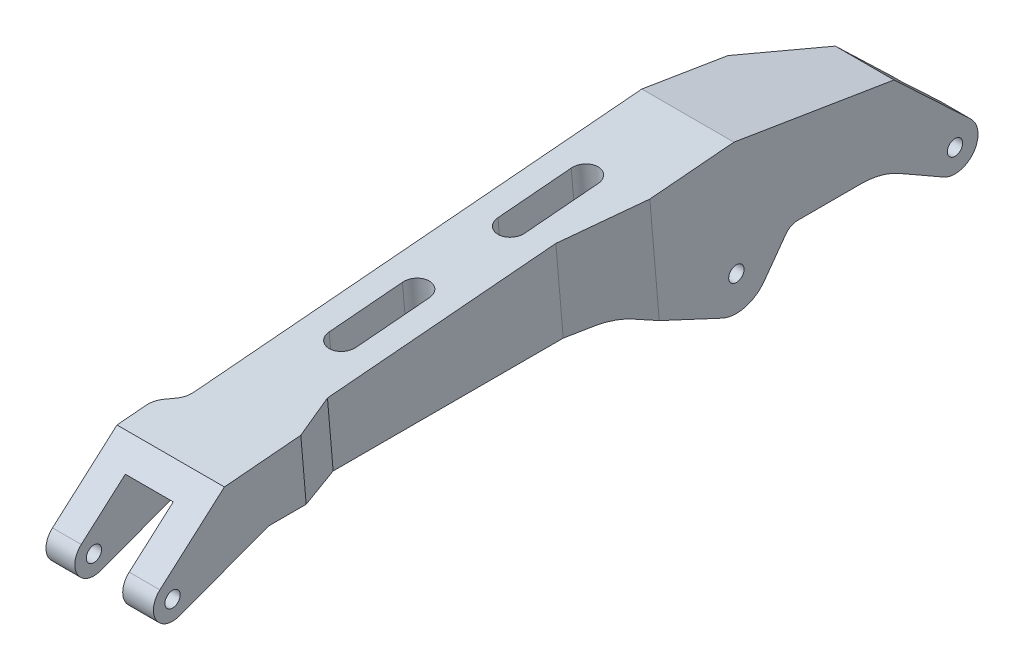
SolidWorks part; units mm, degrees
ref_plane "Plan de face" through (0, 0, 0) normal (0, 0, 1) x (1, 0, 0)
ref_plane "Plan de dessus" through (0, 0, 0) normal (0, 1, 0) x (1, 0, 0)
ref_plane "Plan de droite" through (0, 0, 0) normal (1, 0, 0) x (0, 0, -1)
sketch "Sketch1" plane through (0, 0, 0) normal (1, 0, 0) x (0, 0, -1)
  line L0 (-121.9079, 4) -> (-145.2566, -4.6862)
  line L8 (-34.3077, 4) -> (-121.9079, 4)
  line L12 (-3.8036, -8.1568) -> (-25.8554, 2.1262)
  line L13 (12.8503, 2.4104) -> (7.2926, -5.2742)
  line L15 (32.5383, 4.0311) -> (16.0227, 4.0311)
  line L16 (54.0258, -5.2082) -> (42.4563, 1.3987)
  line L17 (41.089, 23.1881) -> (61.1079, 4.37)
  line L22 (-0.6535, 30.0125) -> (41.089, 23.1881)
  line L24 (-133.4914, 18.5783) -> (-0.6535, 30.0125)
  line L29 (-150.307, 3.7502) -> (-133.4914, 18.5783)
  arc A10 (-25.8554, 2.1262) -> (-34.3077, 4) centre (-34.3077, -16) ccw
  arc A11 (-3.8036, -8.1568) -> (7.2926, -5.2742) centre (0, 0) ccw
  arc A12 (42.4563, 1.3987) -> (32.5383, 4.0311) centre (32.5383, -15.9689) ccw
  arc A13 (54.0258, -5.2082) -> (61.1079, 4.37) centre (57, 0) ccw
  arc A17 (-150.307, 3.7502) -> (-145.2566, -4.6862) centre (-147, 0) ccw
  arc A18 (12.8503, 2.4104) -> (16.0227, 4.0311) centre (16.0227, 0.1161) cw
  circle A19 centre (0, 0) radius 2
  circle A20 centre (57, 0) radius 2
  circle A21 centre (-147, 0) radius 2
  dimension "D1" = 4
  dimension "D2" = 5
  dimension "D3" = 9
  dimension "D4" = 5.9976
  dimension "D5" = 57
  dimension "D6" = 147
  dimension "D7" = 24.9122
  dimension "D8" = 22.4195
  dimension "D9" = 24.3315
  dimension "D10" = 9.4837
  dimension "D11" = 27.475
  dimension "D12" = 42.2967
  dimension "D13" = 21
  dimension "D14" = 13.5
extrude "Boss-Extrude1" add sketch "Sketch1" along normal mid plane 24
sketch "Sketch2" plane through (0, 29.1272, -4.7619) normal (0, 0.9869, -0.1613) x (1, 0, 0)
  line L0 (12, 62.2508) -> (-12, 62.2508) construction
  line L1 (-12, 62.2508) -> (-12, 54.1582) construction
  line L2 (-12, 59.6022) -> (-12, 36.8094) construction
  line L3 (3.5, 62.2508) -> (-12, 62.2508) construction
  line L4 (-12, 62.2508) -> (-12, 54.1582) construction
  line L5 (-12, 59.6022) -> (-12, 36.8094) construction
  line L6 (-12, 36.8094) -> (-12, -5.4873) construction
  line L7 (-12, 36.8094) -> (-12, 17.2508) construction
  line L8 (3.5, 62.2508) -> (3.5, 52.0644)
  line L9 (3.5, 52.0644) -> (-12, 17.2508)
  line L10 (12, 59.6022) -> (12, 36.8094) construction
  line L11 (-12, 17.2508) -> (-12, 62.2508)
  line L12 (-12, 62.2508) -> (3.5, 62.2508)
  dimension "D1" = 8.5
  dimension "D2" = 156
  dimension "D3" = 45
extrude "Cut-Extrude1" cut sketch "Sketch2" against normal through all
sketch "Sketch5" plane through (-12, 0, 0) normal (-1, 0, 0) x (0, 0, 1)
  line L0 (145.2566, -4.6862) -> (121.9079, 4) construction
  line L1 (133.4914, 18.5783) -> (150.307, 3.7502) construction
  line L2 (145.2566, -4.6862) -> (121.9079, 4)
  line L3 (133.4914, 18.5783) -> (150.307, 3.7502)
  line L4 (133.4914, 18.5783) -> (120.4914, 19.6973)
  line L5 (0.6535, 30.0125) -> (133.4914, 18.5783) construction
  line L6 (120.4914, 19.6973) -> (108.9079, 4)
  line L7 (121.9079, 4) -> (34.3077, 4) construction
  line L8 (108.9079, 4) -> (121.9079, 4)
  arc A0 (145.2566, -4.6862) -> (150.307, 3.7502) centre (147, 0) ccw construction
  circle A1 centre (147, 0) radius 2 construction
  arc A2 (145.2566, -4.6862) -> (150.307, 3.7502) centre (147, 0) ccw
  circle A3 centre (147, 0) radius 2
  dimension "D1" = 13
  dimension "D2" = 13
extrude "Boss-Extrude3" add sketch "Sketch5" along normal blind 4
ref_plane "Plane1" through (4, 0, 0) normal (1, 0, 0) x (0, 0, -1)
sketch "Sketch6" plane through (4, 0, 0) normal (1, 0, 0) x (0, 0, -1)
  line L0 (-150.307, 3.7502) -> (-138.8214, 13.8783)
  line L2 (-121.9079, 4) -> (-145.2566, -4.6862)
  line L3 (-145.2566, -4.6862) -> (-121.9079, 4) construction
  line L4 (-133.4914, 18.5783) -> (-150.307, 3.7502) construction
  line L5 (-138.8214, 13.8783) -> (50.9929, 13.8783)
  line L6 (-121.9079, 4) -> (-34.3077, 4) construction
  line L7 (-121.9079, 4) -> (-34.3077, 4)
  line L8 (16.0227, 4.0311) -> (32.5383, 4.0311) construction
  line L9 (7.2926, -5.2742) -> (12.8503, 2.4104) construction
  line L10 (-25.8554, 2.1262) -> (-3.8036, -8.1568) construction
  line L11 (16.0227, 4.0311) -> (32.5383, 4.0311)
  line L12 (7.2926, -5.2742) -> (12.8503, 2.4104)
  line L13 (-25.8554, 2.1262) -> (-3.8036, -8.1568)
  line L14 (61.1079, 4.37) -> (41.089, 23.1881) construction
  line L15 (42.4563, 1.3987) -> (54.0258, -5.2082) construction
  line L16 (61.1079, 4.37) -> (50.9929, 13.8783)
  line L17 (42.4563, 1.3987) -> (54.0258, -5.2082)
  arc A0 (-150.307, 3.7502) -> (-145.2566, -4.6862) centre (-147, 0) ccw construction
  arc A1 (-150.307, 3.7502) -> (-145.2566, -4.6862) centre (-147, 0) ccw
  arc A2 (16.0227, 4.0311) -> (12.8503, 2.4104) centre (16.0227, 0.1161) ccw construction
  arc A3 (-3.8036, -8.1568) -> (7.2926, -5.2742) centre (0, 0) ccw construction
  arc A4 (-25.8554, 2.1262) -> (-34.3077, 4) centre (-34.3077, -16) ccw construction
  arc A5 (16.0227, 4.0311) -> (12.8503, 2.4104) centre (16.0227, 0.1161) ccw
  arc A6 (-3.8036, -8.1568) -> (7.2926, -5.2742) centre (0, 0) ccw
  arc A7 (-25.8554, 2.1262) -> (-34.3077, 4) centre (-34.3077, -16) ccw
  arc A8 (54.0258, -5.2082) -> (61.1079, 4.37) centre (57, 0) ccw construction
  arc A9 (42.4563, 1.3987) -> (32.5383, 4.0311) centre (32.5383, -15.9689) ccw construction
  arc A10 (54.0258, -5.2082) -> (61.1079, 4.37) centre (57, 0) ccw
  arc A11 (42.4563, 1.3987) -> (32.5383, 4.0311) centre (32.5383, -15.9689) ccw
  dimension "D1" = 4.7
extrude "Cut-Extrude2" cut sketch "Sketch6" against normal blind 12.5
chamfer "Chamfer1" distance 3 angle 45 1 edges at (-16, 11.8487, 114.6997)
fillet "Fillet1" radius 4 2 edges at (-12, 11.8487, 114.6997) (-16, 11.6978, 118.3167)
sketch "Sketch7" plane through (0, 29.8476, 2.5692) normal (0, 0.9963, 0.0858) x (1, 0, 0)
  line L2 (0, -97.5373) -> (76.083, -97.5373) construction
  line L10 (12, -111.4064) -> (8, -100.4165)
  line L11 (12, 1.9228) -> (12, -131.4064) construction
  line L12 (8, -100.4165) -> (8, -40.6554)
  line L13 (8, -40.6554) -> (12, -20.0772)
  line L14 (12, -20.0772) -> (12, -111.4064)
  line L15 (12, -131.4064) -> (-16, -131.4064) construction
  dimension "D4" = 4
  dimension "D5" = 20
  dimension "D6" = 22
  dimension "D7" = 169
  dimension "D8" = 160
extrude "Cut-Extrude3" cut sketch "Sketch7" against normal through all
sketch "Sketch8" plane through (0, 29.8476, 2.5692) normal (0, 0.9963, 0.0858) x (1, 0, 0)
  line L0 (-2, -111.4064) -> (-2, 1.9228) construction
  line L1 (-12, 1.9228) -> (-12, -115.2551) construction
  line L2 (8, -40.6554) -> (8, -100.4165) construction
  line L3 (8, -40.6554) -> (8, -100.4165) construction
  line L4 (-12, 1.9228) -> (-12, -115.2551) construction
  line L5 (12, 1.9228) -> (-12, 1.9228) construction
  line L6 (12, 1.9228) -> (-12, 1.9228) construction
  line L7 (12, -111.4064) -> (-12, -111.4064) construction
  line L8 (-2, -86.4064) -> (-2, -67.2418) construction
  line L9 (-2, -42.2418) -> (-2, -23.0772) construction
  line L10 (-5.5, -42.2418) -> (-5.5, -23.0772)
  line L11 (1.5, -42.2418) -> (1.5, -23.0772)
  line L12 (-5.5, -86.4064) -> (-5.5, -67.2418)
  line L13 (1.5, -86.4064) -> (1.5, -67.2418)
  arc A0 (-5.5, -42.2418) -> (1.5, -42.2418) centre (-2, -42.2418) ccw
  arc A1 (1.5, -23.0772) -> (-5.5, -23.0772) centre (-2, -23.0772) ccw
  arc A2 (-5.5, -86.4064) -> (1.5, -86.4064) centre (-2, -86.4064) ccw
  arc A3 (1.5, -67.2418) -> (-5.5, -67.2418) centre (-2, -67.2418) ccw
  point P8 (-2, -32.6595)
  point P20 (-2, -76.8241)
  dimension "D1" = 10
  dimension "D2" = 20
  dimension "D3" = 25
  dimension "D6" = 7
  dimension "D9" = 25
  dimension "D4" = 25
extrude "Cut-Extrude4" cut sketch "Sketch8" against normal through all
equation "\"Longueur1\"= 135mm"
equation "\"Longueur2\"= 147mm"
equation "\"D6@Sketch1\"=\"Longueur2\""
equation "\"D2@Sketch5\"=\"D1@Sketch5\""
equation "\"D1@Sketch8\"=\"D2@Sketch8\"/2"
